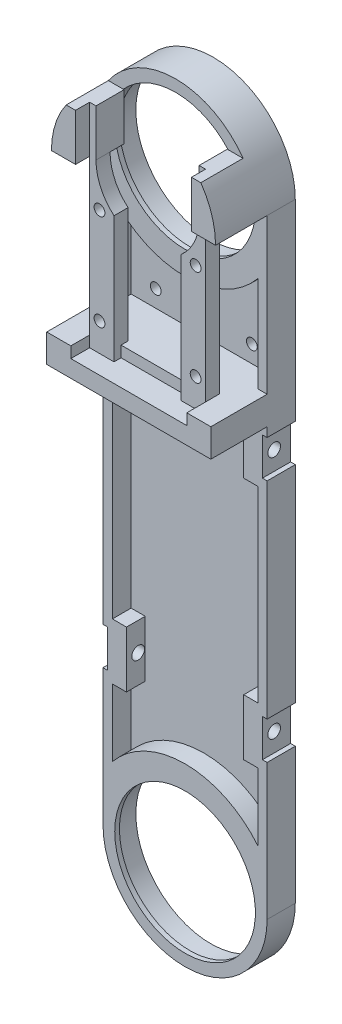
SolidWorks part; units mm, degrees
ref_plane "정면" through (0, 0, 0) normal (0, 0, 1) x (1, 0, 0)
ref_plane "윗면" through (0, 0, 0) normal (0, 1, 0) x (1, 0, 0)
ref_plane "우측면" through (0, 0, 0) normal (1, 0, 0) x (0, 0, -1)
sketch "스케치1" plane through (0, 0, 0) normal (0, 0, 1) x (1, 0, 0)
  line L0 (-17.5, 0) -> (17.5, 0) construction
  line L2 (-17.5, 0) -> (-17.5, 130)
  line L4 (17.5, 0) -> (17.5, 130)
  line L5 (-17.5, 130) -> (17.5, 130) construction
  line L6 (17.5, 130) -> (-17.5, 0) construction
  line L7 (17.5, 0) -> (-17.5, 130) construction
  arc A0 (-17.5, 0) -> (17.5, 0) centre (0, 0) ccw
  arc A1 (17.5, 130) -> (-17.5, 130) centre (0, 130) ccw
  dimension "D1" = 35
  dimension "D2" = 130
extrude "보스-돌출1" add sketch "스케치1" along normal blind 6
sketch "스케치2" plane through (0, 0, 0) normal (0, 0, -1) x (-1, 0, 0)
  circle A0 centre (0, 0) radius 16
  circle A1 centre (0, 130) radius 16
  arc A2 (17.5, 130) -> (-17.5, 130) centre (0, 130) ccw construction
  arc A3 (-17.5, 0) -> (17.5, 0) centre (0, 0) ccw construction
  dimension "D1" = 1.5
  dimension "D2" = 1.5
extrude "컷-돌출1" cut sketch "스케치2" against normal blind 5
chamfer "모따기1" distance 0.5 angle 64 2 edges at (-16, 130, 0) (-16, 0, 0) first distance on face at (-16, 130, 5) first distance on face at (-16, 0, 5)
sketch "스케치24" plane through (0, 0, 5) normal (0, 0, -1) x (-1, 0, 0)
  circle A0 centre (0, 130) radius 15
  circle A1 centre (0, 0) radius 15
  circle A2 centre (0, 130) radius 16 construction
  circle A3 centre (0, 0) radius 16 construction
  dimension "D1" = 1
  dimension "D2" = 1
extrude "컷-돌출15" cut sketch "스케치24" against normal through all
sketch "스케치25" plane through (0, 0, 6) normal (0, 0, 1) x (1, 0, 0)
  line L0 (-15.5, 12.6392) -> (-15.5, 27)
  line L5 (-15.5, 12.6392) -> (15.5, 117.3608) construction
  line L6 (-15.5, 117.3608) -> (15.5, 12.6392) construction
  line L8 (15.5, 12.6392) -> (15.5, 27)
  line L10 (-17.5, 130) -> (-17.5, 0) construction
  line L11 (-15.5, 97) -> (15.5, 97)
  line L15 (-15.5, 27) -> (-12.5, 27)
  line L17 (-15.5, 39) -> (-12.5, 39)
  line L18 (-12.5, 27) -> (-12.5, 39)
  line L19 (15.5, 27) -> (12.5, 27)
  line L21 (15.5, 39) -> (12.5, 39)
  line L22 (12.5, 27) -> (12.5, 39)
  line L27 (17.5, 0) -> (17.5, 130) construction
  line L28 (-15.5, 97) -> (-15.5, 117.3608)
  line L29 (15.5, 97) -> (15.5, 117.3608)
  line L30 (-15.5, 39) -> (-15.5, 79)
  line L31 (15.5, 39) -> (15.5, 79)
  line L32 (-15.5, 79) -> (-12.5, 79)
  line L33 (12.5, 79) -> (15.5, 79)
  line L35 (-12.5, 79) -> (-12.5, 91)
  line L36 (-12.5, 91) -> (12.5, 91)
  line L37 (12.5, 79) -> (12.5, 91)
  arc A0 (-15.5, 117.3608) -> (15.5, 117.3608) centre (0, 130) ccw
  arc A1 (15.5, 12.6392) -> (-15.5, 12.6392) centre (0, 0) ccw
  point P6 (0, 65)
  dimension "D3" = 20
  dimension "D4" = 20
  dimension "D1" = 2
  dimension "D2" = 2
  dimension "D5" = 40
  dimension "D6" = 18
  dimension "D7" = 12
  dimension "D8" = 12
  dimension "D9" = 33
extrude "컷-돌출16" cut sketch "스케치25" against normal blind 4
sketch "스케치26" plane through (0, 0, 6) normal (0, 0, 1) x (1, 0, 0)
  line L0 (-17.5, 130) -> (-17.5, 0) construction
  line L1 (-17.5, 89) -> (-16.5, 89)
  line L2 (-17.5, 89) -> (-17.5, 81)
  line L3 (-17.5, 81) -> (-16.5, 81)
  line L4 (-16.5, 89) -> (-16.5, 81)
  line L5 (17.5, 0) -> (17.5, 130) construction
  line L6 (17.5, 89) -> (16.5, 89)
  line L7 (17.5, 89) -> (17.5, 81)
  line L8 (17.5, 81) -> (16.5, 81)
  line L9 (16.5, 89) -> (16.5, 81)
  line L10 (15.5, 39) -> (15.5, 79) construction
  line L11 (-17.5, 37) -> (-16.5, 37)
  line L12 (-17.5, 37) -> (-17.5, 29)
  line L13 (-17.5, 29) -> (-16.5, 29)
  line L14 (-16.5, 37) -> (-16.5, 29)
  line L15 (17.5, 37) -> (16.5, 37)
  line L16 (17.5, 37) -> (17.5, 29)
  line L17 (17.5, 29) -> (16.5, 29)
  line L18 (16.5, 37) -> (16.5, 29)
  point P24 (15.5, 59)
  dimension "D1" = 44
  dimension "D2" = 22
  dimension "D3" = 8
  dimension "D4" = 1
extrude "컷-돌출17" cut sketch "스케치26" against normal through all
sketch "스케치27" plane through (-16.5, 0, 0) normal (-1, 0, 0) x (0, 0, 1)
  line L0 (3.5, 85) -> (3.5, 33) construction
  line L1 (6, 81) -> (6, 89) construction
  line L2 (0, 89) -> (6, 89) construction
  line L3 (0, 29) -> (6, 29) construction
  circle A0 centre (3.5, 85) radius 1.35
  circle A1 centre (3.5, 33) radius 1.35
  dimension "D1" = 2.5
  dimension "D2" = 4
  dimension "D3" = 4
  dimension "D4" = 2.7
extrude "컷-돌출18" cut sketch "스케치27" against normal through all
sketch "스케치29" plane through (0, 0, 6) normal (0, 0, 1) x (1, 0, 0)
  line L0 (-17.5, 130) -> (-17.5, 89) construction
  line L1 (-17.5, 91) -> (17.5, 91)
  line L2 (-17.5, 91) -> (-17.5, 97)
  line L3 (-17.5, 97) -> (17.5, 97)
  line L4 (17.5, 91) -> (17.5, 97)
  line L6 (-15.5, 97) -> (15.5, 97) construction
  line L7 (17.5, 89) -> (17.5, 130) construction
  dimension "D1" = 6
extrude "보스-돌출3" add sketch "스케치29" along normal blind 12
sketch "스케치30" plane through (0, 0, 6) normal (0, 0, 1) x (1, 0, 0)
  line L0 (-17.5, 130) -> (-15, 130)
  line L1 (15, 130) -> (17.5, 130)
  arc A0 (17.5, 130) -> (-17.5, 130) centre (0, 130) ccw
  arc A1 (15, 130) -> (-15, 130) centre (0, 130) ccw
extrude "보스-돌출4" add sketch "스케치30" along normal blind 2
sketch "스케치31" plane through (0, 0, 8) normal (0, 0, 1) x (1, 0, 0)
  line L0 (-17.5, 130) -> (-11, 130)
  line L1 (11, 130) -> (17.5, 130)
  line L2 (-14.3614, 140) -> (-4.5826, 140)
  line L3 (4.5826, 140) -> (14.3614, 140)
  arc A0 (17.5, 130) -> (14.3614, 140) centre (0, 130) ccw
  arc A1 (11, 130) -> (4.5826, 140) centre (0, 130) ccw
  arc A2 (-14.3614, 140) -> (-17.5, 130) centre (0, 130) ccw
  arc A3 (-4.5826, 140) -> (-11, 130) centre (0, 130) ccw
  dimension "D1" = 22
  dimension "D3" = 17.5
  dimension "D2" = 10
extrude "보스-돌출5" add sketch "스케치31" along normal blind 9
sketch "스케치32" plane through (0, 0, 18) normal (0, 0, 1) x (1, 0, 0)
  line L0 (-16.5, 91) -> (16.5, 91) construction
  line L1 (-12.365, 94.65) -> (12.365, 94.65)
  line L2 (-12.365, 94.65) -> (-12.365, 144.65)
  line L3 (-12.365, 144.65) -> (12.365, 144.65)
  line L4 (12.365, 94.65) -> (12.365, 144.65)
  line L5 (17.5, 89) -> (17.5, 91) construction
  point P6 (0, 144.65)
  dimension "D1" = 50
  dimension "D2" = 24.73
  dimension "D3" = 3.65
  dimension "D4" = 17.5
extrude "컷-돌출19" cut sketch "스케치32" against normal blind 4
sketch "스케치33" plane through (0, 0, 14) normal (0, 0, 1) x (1, 0, 0)
  line L0 (-12.365, 94.65) -> (12.365, 94.65) construction
  line L1 (-7.15, 94.65) -> (7.15, 94.65)
  line L2 (-7.15, 94.65) -> (-7.15, 97)
  line L3 (-7.15, 97) -> (7.15, 97)
  line L4 (7.15, 94.65) -> (7.15, 97)
  line L5 (-12.365, 97) -> (12.365, 97) construction
  arc A0 (-15, 130) -> (15, 130) centre (0, 130) ccw construction
  dimension "D1" = 14.3
  dimension "D2" = 7.15
extrude "컷-돌출20" cut sketch "스케치33" against normal blind 1.5
sketch "스케치34" plane through (0, 97, 0) normal (0, 1, 0) x (1, 0, 0)
  line L0 (-12.365, -14) -> (-7.15, -14) construction
  line L1 (-7.15, -14) -> (-12.365, -14)
  line L2 (-7.15, -14) -> (-7.15, -11)
  line L3 (-7.15, -11) -> (-12.365, -11)
  line L4 (-12.365, -14) -> (-12.365, -11)
  line L5 (-7.15, -12.5) -> (-7.15, -14) construction
  line L6 (7.15, -14) -> (12.365, -14)
  line L7 (7.15, -14) -> (7.15, -11)
  line L8 (7.15, -11) -> (12.365, -11)
  line L9 (12.365, -14) -> (12.365, -11)
  line L10 (-12.365, -18) -> (-12.365, -14) construction
  line L11 (12.365, -14) -> (12.365, -18) construction
  dimension "D1" = 3
extrude "보스-돌출6" add sketch "스케치34" along normal up to next
sketch "스케치35" plane through (0, 0, 14) normal (0, 0, 1) x (1, 0, 0)
  line L0 (14.3614, 140) -> (11.1803, 140) construction
  line L2 (-11, 130) -> (-11, 140)
  line L3 (-11, 140) -> (11, 140)
  line L4 (11, 130) -> (11, 140)
  arc A0 (-11, 130) -> (11, 130) centre (0, 130) ccw
  dimension "D1" = 22
  dimension "D2" = 22
extrude "컷-돌출21" cut sketch "스케치35" against normal blind 6
sketch "스케치36" plane through (0, 0, 14) normal (0, 0, 1) x (1, 0, 0)
  line L1 (-10.25, 100.65) -> (10.25, 100.65) construction
  line L2 (-10.25, 100.65) -> (-10.25, 121.15) construction
  line L3 (-10.25, 121.15) -> (10.25, 121.15) construction
  line L4 (10.25, 100.65) -> (10.25, 121.15) construction
  line L5 (-12.365, 94.65) -> (12.365, 94.65) construction
  arc A0 (-15, 130) -> (15, 130) centre (0, 130) ccw construction
  circle A1 centre (-10.25, 121.15) radius 1.15
  circle A2 centre (10.25, 121.15) radius 1.15
  circle A3 centre (-10.25, 100.65) radius 1.15
  circle A4 centre (10.25, 100.65) radius 1.15
  dimension "D5" = 2.3
  dimension "D1" = 20.5
  dimension "D2" = 10.25
  dimension "D3" = 20.5
  dimension "D4" = 6
extrude "컷-돌출22" cut sketch "스케치36" against normal through all
